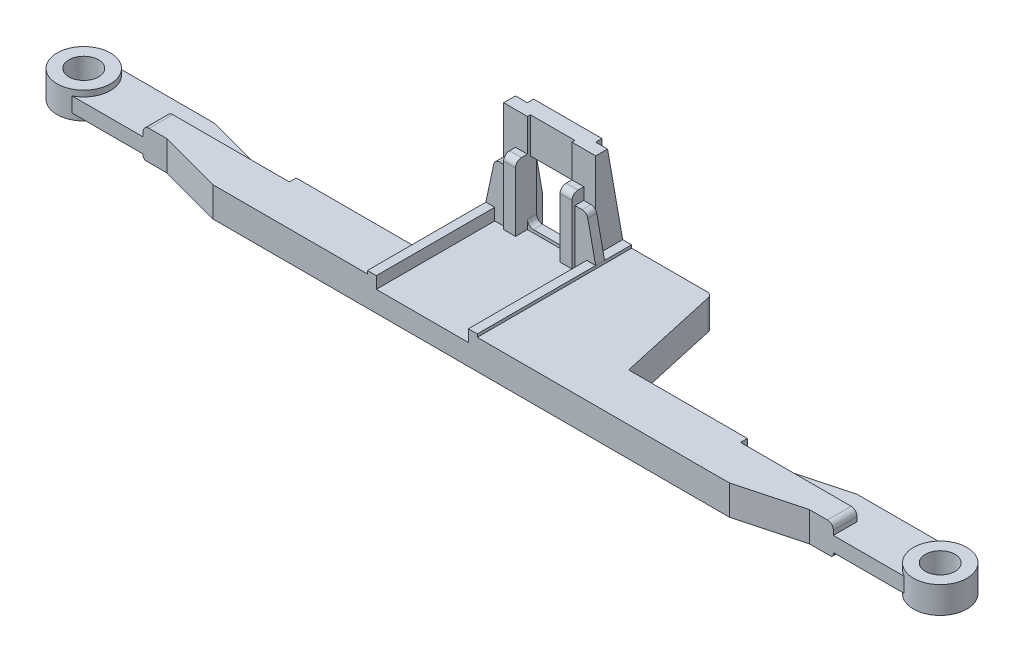
SolidWorks part; units mm, degrees
material "ABS PC"
ref_plane "Piano frontale" through (0, 0, 0) normal (0, 0, 1) x (1, 0, 0)
ref_plane "Piano superiore" through (0, 0, 0) normal (0, 1, 0) x (1, 0, 0)
ref_plane "Piano destro" through (0, 0, 0) normal (1, 0, 0) x (0, 0, -1)
sketch "Schizzo1" plane through (0, 0, 0) normal (0, 1, 0) x (1, 0, 0)
  line L0 (0, 0) -> (-121.1472, 0) construction
  line L1 (43.5, 0) -> (-43.5, 0)
  line L3 (-43.5, 0) -> (-54.1252, 2.847)
  line L4 (-54.1252, 2.847) -> (-72.1252, 2.847)
  line L5 (43.5, 0) -> (54.1252, 2.847)
  line L6 (54.1252, 2.847) -> (72.1252, 2.847)
  line L7 (0, 0) -> (119.0724, 0) construction
  line L8 (-72.1252, 10.847) -> (-54.1252, 10.847)
  line L9 (-54.1252, 10.847) -> (-43.5, 8)
  line L10 (-43.5, 8) -> (43.5, 8)
  line L11 (-43.5, 0) -> (-43.5, 8) construction
  line L12 (54.1252, 10.847) -> (72.1252, 10.847)
  line L13 (-72.1252, 2.847) -> (-72.1252, 6.847) construction
  line L14 (-54.1252, 2.847) -> (-54.1252, 10.847) construction
  line L15 (43.5, 8) -> (54.1252, 10.847)
  line L16 (43.5, 0) -> (43.5, 8) construction
  arc A0 (-72.1252, 10.847) -> (-72.1252, 2.847) centre (-72.1252, 6.847) ccw
  arc A1 (72.1252, 2.847) -> (72.1252, 10.847) centre (72.1252, 6.847) ccw
  circle A2 centre (-72.1252, 6.847) radius 2.5
  circle A3 centre (72.1252, 6.847) radius 2.5
  point P6 (0, 0)
  dimension "D2" = 8
  dimension "D5" = 8
  dimension "D13" = 5
  dimension "D14" = 5
  dimension "D1" = 87
  dimension "D3" = 15
  dimension "D4" = 15
  dimension "D6" = 18
  dimension "D7" = 18
  dimension "D8" = 11
  dimension "D9" = 11
  dimension "D10" = 11
  dimension "D11" = 8
  dimension "D12" = 11
extrude "Estrusione-Estrusione1" add sketch "Schizzo1" along normal mid plane 2.5
sketch "Schizzo2" plane through (0, 0, 0) normal (0, 1, 0) x (1, 0, 0)
  circle A0 centre (-72.1252, 6.847) radius 4.5
  circle A1 centre (-72.1252, 6.847) radius 2.5
  point P4 (0, 0)
  dimension "D1" = 9
  dimension "D2" = 5
extrude "Estrusione-Estrusione2" add sketch "Schizzo2" along normal mid plane 4.5
mirror "Specchia1" about plane through (0, 0, 0) normal (1, 0, 0) of "Estrusione-Estrusione2"
sketch "Schizzo7" plane through (0, 0, 0) normal (0, 1, 0) x (1, 0, 0)
  line L0 (-17.5, 8) -> (-17.5, 26)
  line L1 (43.5, 8) -> (-43.5, 8) construction
  line L2 (-17.5, 26) -> (14.5, 26)
  line L3 (14.5, 26) -> (18.5, 8)
  line L5 (-17.5, 8) -> (-37.5, 8)
  line L6 (-37.5, 8) -> (-37.5, 6.847)
  line L7 (-37.5, 6.847) -> (-58.1252, 6.847)
  line L9 (-54.1252, 2.847) -> (-43.5, 0)
  line L10 (-43.5, 0) -> (43.5, 0)
  line L11 (-43.5, 0) -> (43.5, 0) construction
  line L12 (43.5, 0) -> (54.1252, 2.847)
  line L13 (54.1252, 2.847) -> (58.1252, 2.847)
  line L14 (54.1252, 2.847) -> (70.0636, 2.847) construction
  line L15 (58.1252, 2.847) -> (58.1252, 6.847)
  line L16 (58.1252, 6.847) -> (38.5, 6.847)
  line L17 (38.5, 6.847) -> (38.5, 8)
  line L18 (38.5, 8) -> (18.5, 8)
  line L19 (-54.1252, 2.847) -> (-58.1252, 2.847)
  line L20 (-70.0636, 2.847) -> (-54.1252, 2.847) construction
  line L21 (-58.1252, 2.847) -> (-58.1252, 6.847)
  point P4 (38.9782, 6.847)
  point P31 (57.1419, 2.847)
  point P32 (54.1252, 2.847)
  point P33 (0, 0)
  point P35 (57.0719, 2.847)
  dimension "D1" = 26
  dimension "D2" = 25
  dimension "D3" = 32
  dimension "D4" = 20
  dimension "D5" = 20
  dimension "D6" = 4
  dimension "D7" = 4
  dimension "D8" = 4
  dimension "D9" = 4
extrude "Estrusione-Estrusione3" add sketch "Schizzo7" along normal blind 3 and the other way blind 2 contours L2 L3 L18 L17 L16 L15 L13 L12 L10 L9 L19 L21 L7 L6 L5 L0
fillet "Raccordo1" radius 1 1 edges at (-58.1252, 3, -4.847)
fillet "Raccordo2" radius 1 1 edges at (58.1252, 3, -4.847)
sketch "Schizzo8" plane through (0, 3, 0) normal (0, 1, 0) x (1, 0, 0)
  line L0 (-17.5, 0) -> (-17.5, 26)
  line L1 (-43.5, 0) -> (43.5, 0) construction
  line L2 (-17.5, 26) -> (14.5, 26) construction
  line L3 (-17.5, 8) -> (-17.5, 26) construction
  line L4 (-17.5, 26) -> (-16, 26)
  line L5 (-16, 26) -> (-16, 0)
  line L6 (-16, 0) -> (-17.5, 0)
  dimension "D1" = 1.5
extrude "Estrusione-Estrusione4" add sketch "Schizzo8" along normal blind 0.5
sketch "Schizzo9" plane through (0, 3, 0) normal (0, 1, 0) x (1, 0, 0)
  line L0 (1, 26) -> (1, 0)
  line L1 (-16, 26) -> (14.5, 26) construction
  line L2 (-16, 0) -> (43.5, 0) construction
  line L3 (1, 0) -> (-0.5, 0)
  line L4 (-0.5, 0) -> (-0.5, 26)
  line L5 (-0.5, 26) -> (1, 26)
  line L6 (-16, 0) -> (-16, 26) construction
  point P6 (0, 0)
  dimension "D1" = 1.5
  dimension "D2" = 15.5
extrude "Estrusione-Estrusione5" add sketch "Schizzo9" along normal blind 0.5
sketch "Schizzo10" plane through (0, 3, 0) normal (0, 1, 0) x (1, 0, 0)
  line L1 (-16, 26) -> (-0.5, 26)
  line L2 (-16, 26) -> (-16, 0)
  line L3 (-16, 0) -> (-0.5, 0)
  line L4 (-0.5, 26) -> (-0.5, 0)
extrude "Taglio-Estrusione1" cut sketch "Schizzo10" against normal blind 1.5
sketch "Schizzo11" plane through (-16, 0, 0) normal (1, 0, 0) x (0, 0, -1)
  line L0 (26, 1.5) -> (26, 3.5)
  line L1 (23.4433, 18) -> (21.4433, 18)
  line L2 (21.4433, 18) -> (21.4433, 1.5)
  line L3 (26, 3.5) -> (23.4433, 18)
  line L5 (21.4433, 1.5) -> (26, 1.5)
  line L6 (26, 3.5) -> (26, 1.5) construction
  line L7 (26, 1.5) -> (0, 1.5) construction
  line L8 (26, -2) -> (8, -2) construction
  point P2 (21.627, 1.5)
  dimension "D1" = 10
  dimension "D2" = 2
  dimension "D3" = 20
extrude "Estrusione-Estrusione6" add sketch "Schizzo11" along normal blind 2 contours L5 L0 L3 L1 L2
sketch "Schizzo12" plane through (-0.5, 0, 0) normal (-1, 0, 0) x (0, 0, 1)
  line L0 (-26, 1.5) -> (-26, 3.5)
  line L1 (-26, 3.5) -> (-26, 1.5) construction
  line L2 (-26, -2) -> (-26, 3) construction
  line L3 (-26, 3.5) -> (-23.4433, 18)
  line L5 (-21.4433, 1.5) -> (-26, 1.5)
  line L6 (0, 1.5) -> (-26, 1.5) construction
  line L7 (-23.4433, 18) -> (-21.4433, 18)
  line L8 (-21.4433, 18) -> (-21.4433, 1.5)
  point P6 (-21.6756, 1.5)
  dimension "D1" = 10
  dimension "D2" = 20
  dimension "D3" = 2
extrude "Estrusione-Estrusione7" add sketch "Schizzo12" along normal blind 2
sketch "Schizzo15" plane through (-2.5, 0, 0) normal (-1, 0, 0) x (0, 0, 1)
  line L0 (-23.4433, 18) -> (-26, 3.5) construction
  line L1 (-21.4433, 1.5) -> (-23.0012, 1.5)
  line L2 (-21.4433, 1.5) -> (-21.4433, 18)
  line L3 (-21.4433, 18) -> (-23.4433, 18)
  line L4 (-23.0012, 1.5) -> (-23.0012, 12)
  line L5 (-23.4433, 18) -> (-24.5012, 18)
  line L7 (-23.0012, 12) -> (-24.5012, 12)
  line L8 (-24.5012, 18) -> (-24.5012, 12)
  point P9 (0, 0)
  point P10 (0, 0)
  point P11 (0, 0)
  dimension "D1" = 6
  dimension "D2" = 1.5
extrude "Estrusione-Estrusione8" add sketch "Schizzo15" along normal up to surface (11.5 mm away) up to face at (-14, 8.5, -23.666)
sketch "Schizzo16" plane through (0, 0, -21.4433) normal (0, 0, 1) x (1, 0, 0)
  line L1 (-16, 18) -> (-16, 3.5) construction
  line L3 (-0.5, 3.5) -> (-0.5, 18) construction
  line L4 (-14, 12) -> (-2.5, 12)
  line L5 (-14, 18) -> (-14, 12)
  line L6 (-2.5, 18) -> (-14, 18)
  line L7 (-2.5, 12) -> (-2.5, 18)
  line L8 (-12, 12) -> (-4.5, 12)
  line L9 (-12, 18) -> (-12, 12)
  line L10 (-4.5, 18) -> (-12, 18)
  line L11 (-4.5, 12) -> (-4.5, 18)
  dimension "D2" = 4
  dimension "D3" = 4
  dimension "D1" = 0
extrude "Taglio-Estrusione2" cut sketch "Schizzo16" against normal blind 0.5
sketch "Schizzo17" plane through (0, 0, -21.4433) normal (0, 0, 1) x (1, 0, 0)
  line L0 (-12, 12) -> (-4.5, 12) construction
  line L2 (-12, 12) -> (-4.5, 12)
  line L3 (-12, 12) -> (-12, 3)
  line L4 (-11, 2) -> (-5.5, 2)
  line L5 (-4.5, 12) -> (-4.5, 3)
  line L9 (-16, 1.5) -> (-0.5, 1.5) construction
  line L15 (-14, 12) -> (-2.5, 12)
  line L16 (-14, 18) -> (-14, 12)
  line L17 (-2.5, 18) -> (-14, 18)
  line L18 (-2.5, 12) -> (-2.5, 18)
  line L19 (-14, 12) -> (-2.5, 12) construction
  line L20 (-14, 18) -> (-14, 12) construction
  line L21 (-2.5, 18) -> (-14, 18) construction
  line L22 (-2.5, 12) -> (-2.5, 18) construction
  arc A0 (-5.5, 2) -> (-4.5, 3) centre (-5.5, 3) ccw
  arc A1 (-12, 3) -> (-11, 2) centre (-11, 3) ccw
  point P0 (-8.25, 12)
  point P7 (0, 0)
  point P9 (0, 0)
  point P12 (0, 0)
  point P17 (0, 0)
  point P20 (-12.1242, 8.5036)
  point P21 (0, 0)
  point P22 (0, 0)
  point P27 (-14.0747, 12.0017)
  dimension "D1" = 1
  dimension "D2" = 2
  dimension "D3" = 0.5
  dimension "D4" = 0
extrude "Taglio-Estrusione3" cut sketch "Schizzo17" against normal through all
sketch "Schizzo18" plane through (0, 0, -21.4433) normal (0, 0, 1) x (1, 0, 0)
  line L3 (-12, 18) -> (-12, 3) construction
  line L4 (-12, 12.5) -> (-14, 12.5)
  line L5 (-12, 12.5) -> (-12, 1.5)
  line L6 (-12, 1.5) -> (-14, 1.5)
  line L7 (-14, 12.5) -> (-14, 1.5)
  line L9 (-16, 1.5) -> (-0.5, 1.5) construction
  line L10 (-12, 12) -> (-4.5, 12) construction
  point P11 (0, 0)
  point P14 (0, 0)
  point P16 (0, 0)
  point P18 (-14.5478, 13.3279)
  dimension "D1" = 0.5
  dimension "D2" = 2
extrude "Estrusione-Estrusione13" add sketch "Schizzo18" along normal blind 2
fillet "Raccordo3" radius 1 1 edges at (-13, 12.5, -19.4433)
ref_plane "Piano1" through (-8.25, 0, 0) normal (1, 0, 0) x (0, 0, -1)
mirror "Specchia3" about plane through (-8.25, 0, 0) normal (1, 0, 0) of "Raccordo3", "Estrusione-Estrusione13"
sketch3d "Schizzo3D2"
  line L0 (-14, 12.5, -21.4433) -> (-14, 1.5, -21.4433) construction
  line L1 (-14, 10.5, -21.4433) -> (-16, 10.5, -21.4433)
  line L4 (-16, 1.5, -21.4433) -> (-14, 1.5, -21.4433)
  line L5 (-14, 1.5, -21.4433) -> (-14, 10.5, -21.4433)
  line L6 (-17.5, 3.5, -26) -> (-17.5, 3.5, 0) construction
  line L7 (-16, 1.5, -21.4433) -> (-16, 3.5, -21.4433)
  line L8 (-16, 3.5, -21.4433) -> (-17.5, 3.5, -21.4433)
  line L9 (-12, 12.5, -21.4433) -> (-14, 12.5, -21.4433) construction
  line L10 (-16, 10.5, -21.4433) -> (-17.5, 3.5, -21.4433)
  line L12 (-16, 3.5, -26) -> (-17.5, 3.5, -26) construction
  point P5 (-17.5, 3.5, -21.4433)
  point P10 (-14.8528, 10.5, -21.4433)
  dimension "D1" = 2
  dimension "D2" = 2
extrude "Estrusione-Estrusione14" add sketch "Schizzo3D2" along direction (0, 0, -1) on the side of the normal blind 1.5 contours L8 L10 L1 L5 L4 L7
fillet "Raccordo4" radius 1 1 edges
mirror "Specchia4" about plane through (-8.25, 0, 0) normal (1, 0, 0) of "Estrusione-Estrusione14", "Raccordo4"
fillet "Raccordo5" radius 0.5 1 edges at (58.1252, -2, -4.847)
fillet "Raccordo6" radius 0.5 1 edges at (-58.1252, -2, -4.847)
shell "Svuota1" thickness 1 removed face at (0, -2, -7.6735)
sketch "Schizzo19" plane through (0, 1.5, 0) normal (0, 1, 0) x (1, 0, 0)
  line L4 (-14, 26) -> (-14, 23.0012)
  line L5 (-14, 23.0012) -> (-2.5, 23.0012)
  line L6 (-2.5, 23.0012) -> (-2.5, 26)
  line L7 (-2.5, 26) -> (-14, 26)
  line L8 (-14, 26) -> (-14, 23.0012)
  line L9 (-14, 23.0012) -> (-2.5, 23.0012)
  line L10 (-2.5, 23.0012) -> (-2.5, 26)
  line L11 (-2.5, 26) -> (-14, 26)
  dimension "D1" = 0
extrude "Taglio-Estrusione4" cut sketch "Schizzo19" against normal through all
ref_plane "Piano2" through (0, 0, -20.9433) normal (0, 0, 1) x (-1, 0, 0)
sketch "Schizzo20" plane through (0, 0, -20.9433) normal (0, 0, 1) x (-1, 0, 0)
  line L0 (16.5, -0.5) -> (16.5, 2)
  line L1 (16.5, -0.5) -> (13, -0.5) construction
  line L2 (16.5, 2) -> (8.5, 2)
  line L3 (8.5, 2) -> (8.5, 5)
  line L4 (8.5, 5) -> (3.5, 5)
  line L5 (3.5, 5) -> (3.5, 9)
  line L6 (3.5, 9) -> (-3.5, 9)
  line L7 (-3.5, 9) -> (-3.5, 5)
  line L8 (-3.5, 5) -> (-9.5, 5)
  line L9 (-9.5, 5) -> (-9.5, 2)
  line L10 (-9.5, 2) -> (-15.5, 2)
  line L11 (-15.5, 2) -> (-15.5, -2)
  line L12 (-15.5, -2) -> (-0.5, -2)
  line L13 (-0.5, -2) -> (-0.5, -0.5)
  line L14 (-0.5, -0.5) -> (16.5, -0.5)
  line L15 (2.5, 2) -> (-14.5, 2) construction
  line L18 (16.5, 2) -> (16.5, -0.5) construction
  line L22 (-0.5, -2) -> (0, -2) construction
  line L25 (-9.5, 2) -> (-16.0298, 2) construction
  dimension "D1" = 3
  dimension "D2" = 4
  dimension "D3" = 7
  dimension "D4" = 5
  dimension "D5" = 6
  dimension "D6" = 8
  dimension "D7" = 6
extrude "Estrusione-Estrusione17" add sketch "Schizzo20" along normal blind 1.5 contours L10 L11 L12 L13 L14 L0 L2 L3 L4 L5 L6 L7 L8 L9
sketch "Schizzo24" plane through (0, 0, -19.4433) normal (0, 0, 1) x (1, 0, 0)
  line L0 (0.5, 0.5) -> (-16.5, 0.5) construction
  line L1 (-8.5, -2) -> (-6.5, -2)
  line L2 (-8.5, -2) -> (-8.5, 0.5)
  line L3 (-8.5, 0.5) -> (-6.5, 0.5)
  line L4 (-6.5, -2) -> (-6.5, 0.5)
  line L5 (-16.5, -2) -> (-8.5, -2) construction
  dimension "D1" = 2
extrude "Estrusione-Estrusione19" add sketch "Schizzo24" along normal up to surface (18.4433 mm away)
sketch "Schizzo25" plane through (0, 0, -19.4433) normal (0, 0, 1) x (1, 0, 0)
  line L0 (0.5, 2) -> (14.9327, 2) construction
  line L1 (9.5, -2) -> (7.5, -2)
  line L2 (9.5, -2) -> (9.5, 2)
  line L3 (9.5, 2) -> (7.5, 2)
  line L4 (7.5, -2) -> (7.5, 2)
  dimension "D1" = 2
extrude "Estrusione-Estrusione20" add sketch "Schizzo25" along normal up to surface (18.4433 mm away)
fillet "Raccordo7" radius 1 1 edges at (14.5, 0.5, -26)
